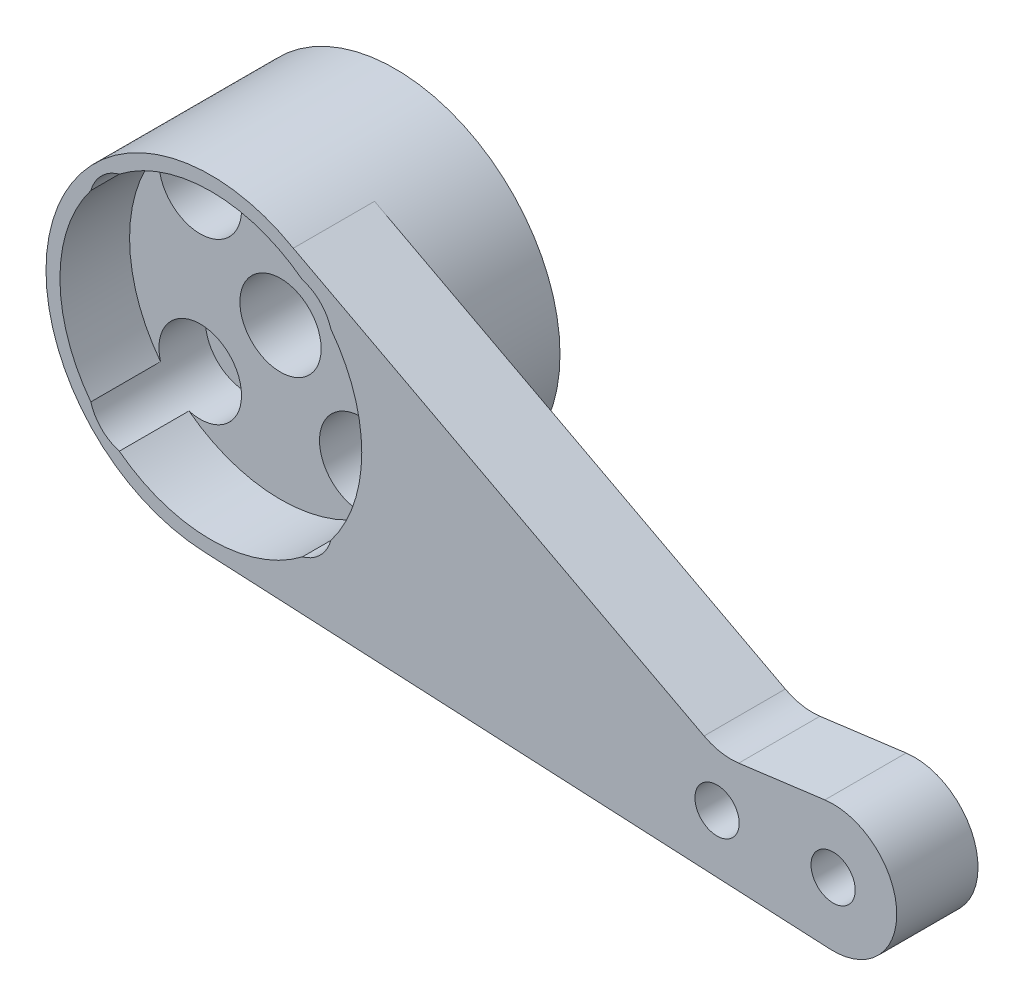
SolidWorks part; units mm, degrees
ref_plane "Front Plane" through (0, 0, 0) normal (0, 0, 1) x (1, 0, 0)
ref_plane "Top Plane" through (0, 0, 0) normal (0, 1, 0) x (1, 0, 0)
ref_plane "Right Plane" through (0, 0, 0) normal (1, 0, 0) x (0, 0, -1)
ref_plane "Plane1" through (0, 0, 0) normal (0, 0, -1) x (-1, 0, 0)
sketch "Sketch1" plane through (0, 0, 0) normal (0, 0, -1) x (-1, 0, 0)
  line L0 (-54.9006, 0.2614) -> (-46.1167, 9.6815) construction
  line L1 (-54.6285, -5.2121) -> (-0.5934, -2.5259)
  line L3 (-54.9006, 0.2614) -> (-1.2984, 11.6566) construction
  line L4 (-8.3993, 23.9536) -> (-43.781, 5.2606)
  line L5 (-46.7655, 4.7237) -> (-54.1894, 5.6953)
  circle A0 centre (-46.1167, 9.6815) radius 4 construction
  arc A2 (-54.1894, 5.6953) -> (-54.6285, -5.2121) centre (-54.9006, 0.2614) ccw
  arc A3 (-0.5934, -2.5259) -> (-8.3993, 23.9536) centre (-1.2984, 11.6566) ccw
  arc A4 (-46.7655, 4.7237) -> (-43.781, 5.2606) centre (-46.1167, 9.6815) ccw
  dimension "D2" = 14.2
  dimension "D3" = 12.88
  dimension "D5" = 35
  dimension "D6" = 8
  dimension "D7" = 10
  dimension "D1" = 54.8
extrude "Boss-Extrude1" add sketch "Sketch1" against normal blind 15
sketch "Sketch10" plane through (0, 0, 0) normal (0, 0, -1) x (-1, 0, 0)
  circle A0 centre (-1.2984, 11.6566) radius 14.2
  arc A1 (-0.5934, -2.5259) -> (-8.3993, 23.9536) centre (-1.2984, 11.6566) ccw construction
  circle A2 centre (-54.9006, 0.2614) radius 5.4803
  arc A3 (-54.1894, 5.6953) -> (-54.6285, -5.2121) centre (-54.9006, 0.2614) ccw construction
  point P5 (-1.2984, 11.6566)
hole_wizard "CBORE for M6 Hex Head Bolt1" positions "Sketch7" profile "Sketch6" counterbore size "M6" standard "Ansi Metric" end condition through all
sketch "Sketch7" plane through (0, 0, 0) normal (0, 0, -1) x (-1, 0, 0)
  point P0 (-1.2984, 11.6566)
sketch "Sketch6" plane through (1.2984, 11.6566, 0) normal (1, 0, 0) x (0, 1, 0)
  line L0 (0, 0) -> (0, 15)
  line L1 (0, 15) -> (3.5, 15)
  line L3 (3.5, 15) -> (3.5, 3)
  line L4 (3.5, 3) -> (12.8, 3)
  line L5 (12.8, 3) -> (12.8, 0)
  line L7 (12.8, 0) -> (0, 0)
  line L11 (0, -6.35) -> (0, 107.95) construction
  dimension "Thru Hole Dia." = 7
  dimension "Thru Hole Depth" = 15
  dimension "C'Bore Dia." = 25.6
  dimension "C'Bore Depth" = 3
ref_plane "Plane4" through (0, 0, 7.5) normal (0, 0, -1) x (-1, 0, 0)
sketch "Sketch30" plane through (0, 0, 15) normal (0, 0, 1) x (1, 0, 0)
  line L1 (68.7065, -22.2417) -> (-19.1857, -22.2417)
  line L2 (68.7065, -22.2417) -> (68.7065, 41.145)
  line L3 (68.7065, 41.145) -> (-19.1857, 41.145)
  line L4 (-19.1857, -22.2417) -> (-19.1857, 41.145)
extrude "Cut-Extrude8" cut sketch "Sketch30" against normal blind 0.125
sketch "Sketch31" plane through (0, 0, 0) normal (0, 0, -1) x (-1, 0, 0)
  line L1 (-64.611, 30.1264) -> (17.734, 30.1264)
  line L2 (-64.611, 30.1264) -> (-64.611, -8.8981)
  line L3 (-64.611, -8.8981) -> (17.734, -8.8981)
  line L4 (17.734, 30.1264) -> (17.734, -8.8981)
extrude "Cut-Extrude9" cut sketch "Sketch31" against normal blind 0.125
sketch "Sketch38" plane through (0, 0, 14.875) normal (0, 0, 1) x (1, 0, 0)
  circle A0 centre (1.2984, 11.6566) radius 3.5 construction
  circle A1 centre (1.2984, 11.6566) radius 3.5
  circle A2 centre (-5.616, 18.5718) radius 1.905
  circle A3 centre (8.2136, 18.571) radius 1.905
  circle A4 centre (8.2128, 4.7414) radius 1.905
  circle A5 centre (-5.6168, 4.7422) radius 1.905
  line B0 (3.7785, 13.3445) -> (3.7783, 9.9684)
  line B1 (-14.7035, 12.2926) -> (-1.6336, 12.2918)
  line B2 (-14.7033, 16.4201) -> (-14.7035, 12.2926)
  line B3 (-11.9069, 16.4199) -> (-14.7033, 16.4201)
  line B4 (-11.2749, 6.8948) -> (-11.2749, 6.8267)
  line B5 (-14.7039, 6.8951) -> (-11.2749, 6.8948)
  line B6 (-14.7036, 11.0226) -> (-14.7039, 6.8951)
  line B7 (-1.6336, 11.0218) -> (-14.7036, 11.0226)
  arc B8 (2.6475, 8.977) -> (3.7783, 9.9684) centre (2.7783, 9.9684) ccw
  arc B9 (3.7785, 13.3445) -> (2.6478, 14.336) centre (2.7785, 13.3446) ccw
  arc B10 (2.6478, 14.336) -> (-1.6336, 12.2918) centre (1.2984, 11.6566) ccw
  arc B11 (-11.9069, 16.4199) -> (-8.9599, 19.0076) centre (-11.9068, 19.3917) ccw
  arc B12 (-4.0299, 21.5478) -> (-8.9599, 19.0076) centre (-5.616, 18.5718) ccw
  arc B13 (-4.0299, 21.5478) -> (-1.7731, 21.3412) centre (-2.6561, 24.1255) ccw
  arc B14 (4.3711, 21.3408) -> (-1.7731, 21.3412) centre (1.2984, 11.6566) ccw
  arc B15 (4.3711, 21.3408) -> (6.628, 21.5471) centre (5.2545, 24.1251) ccw
  arc B16 (11.1896, 16.985) -> (6.628, 21.5471) centre (8.2136, 18.571) ccw
  arc B17 (11.1896, 16.985) -> (10.983, 14.7281) centre (13.7674, 15.6111) ccw
  arc B18 (10.9827, 8.5839) -> (10.983, 14.7281) centre (1.2984, 11.6566) ccw
  arc B19 (10.9827, 8.5839) -> (11.189, 6.3271) centre (13.7669, 7.7006) ccw
  arc B20 (6.6268, 1.7654) -> (11.189, 6.3271) centre (8.2128, 4.7414) ccw
  arc B21 (6.6268, 1.7654) -> (4.3699, 1.972) centre (5.253, -0.8123) ccw
  arc B22 (-1.7742, 1.9724) -> (4.3699, 1.972) centre (1.2984, 11.6566) ccw
  arc B23 (-1.7742, 1.9724) -> (-4.0311, 1.7661) centre (-2.6576, -0.8119) ccw
  arc B24 (-8.9608, 4.3068) -> (-4.0311, 1.7661) centre (-5.6168, 4.7422) ccw
  arc B25 (-8.9608, 4.3068) -> (-11.2749, 6.8267) centre (-11.9077, 3.9231) ccw
  arc B26 (-1.6336, 11.0218) -> (2.6475, 8.977) centre (1.2984, 11.6566) ccw
  dimension "D1" = 3.81
sketch_block_instance "Block1-1"
sketch_block "Block1"
extrude "Cut-Extrude10" cut sketch "Sketch38" against normal through all contours A2 | A3 | A4 | A5
sketch "Sketch39" plane through (0, 0, 0.125) normal (0, 0, -1) x (-1, 0, 0)
  circle A1 centre (-1.2984, 11.6566) radius 12.8 construction
  circle A2 centre (-1.2984, 11.6566) radius 12.8
extrude "Cut-Extrude11" cut sketch "Sketch39" against normal offset from surface (7.75 mm away) 7 flip side to cut contours A2 up to face at (-3.7118, 4.7422, 14.875)
sketch "Sketch40" plane through (0, 0, 14.875) normal (0, 0, 1) x (1, 0, 0)
  circle A0 centre (1.2984, 11.6566) radius 13
  dimension "D1" = 26
extrude "Cut-Extrude12" cut sketch "Sketch40" against normal offset from surface (6 mm away) 1 up to face at (32.9108, 6.1436, 7.875)
sketch "Sketch41" plane through (0, 0, 3) normal (0, 0, -1) x (-1, 0, 0)
  circle A1 centre (-1.2984, 11.6566) radius 12.8
  circle A4 centre (-1.2984, 11.6566) radius 12.8
  dimension "D1" = 0
extrude "Boss-Extrude2" add sketch "Sketch41" along normal blind 4
sketch "Sketch42" plane through (0, 0, 3) normal (0, 0, 1) x (1, 0, 0)
  circle A0 centre (8.2128, 4.7414) radius 1.905 construction
  circle A1 centre (1.2984, 11.6566) radius 3.5
  circle A2 centre (1.2984, 11.6566) radius 3.5
  circle A3 centre (-5.6168, 4.7422) radius 1.905 construction
  circle A4 centre (-5.616, 18.5718) radius 1.905 construction
  circle A5 centre (8.2136, 18.571) radius 1.905 construction
  circle A6 centre (8.2128, 4.7414) radius 1.905
  circle A7 centre (-5.6168, 4.7422) radius 1.905
  circle A8 centre (-5.616, 18.5718) radius 1.905
  circle A9 centre (8.2136, 18.571) radius 1.905
  dimension "D1" = 0
extrude "Cut-Extrude13" cut sketch "Sketch42" against normal through all
sketch "Sketch43" plane through (0, 0, 7.875) normal (0, 0, -1) x (-1, 0, 0)
  circle A0 centre (-1.2984, 11.6566) radius 12.8
  circle A1 centre (-1.2984, 11.6566) radius 14.2
extrude "Boss-Extrude3" add sketch "Sketch43" along normal through all
sketch "Sketch44" plane through (0, 0, 8.875) normal (0, 0, 1) x (1, 0, 0)
  circle A0 centre (8.2136, 18.571) radius 3.556
  circle A1 centre (-5.616, 18.5718) radius 3.556
  circle A2 centre (-5.6168, 4.7422) radius 3.556
  circle A3 centre (8.2128, 4.7414) radius 3.556
  dimension "D1" = 7.112
extrude "Cut-Extrude14" cut sketch "Sketch44" along normal through all and the other way blind 4
sketch "Sketch45" plane through (0, 0, 7.875) normal (0, 0, -1) x (-1, 0, 0)
  line L0 (-54.9006, 0.2614) -> (-44.9006, 0.2614) construction
  circle A0 centre (-54.9006, 0.2614) radius 1.905
  circle A1 centre (-44.9006, 0.2614) radius 1.905
  arc A2 (-54.1894, 5.6953) -> (-54.6285, -5.2121) centre (-54.9006, 0.2614) ccw construction
  dimension "D1" = 3.81
  dimension "D2" = 10
extrude "Cut-Extrude15" cut sketch "Sketch45" against normal through all
sketch "Sketch46" plane through (0, 0, 7.875) normal (0, 0, -1) x (-1, 0, 0)
  circle A0 centre (-54.9006, 0.2614) radius 3.556
  circle A1 centre (-44.9006, 0.2614) radius 3.556
  dimension "D1" = 7.112
extrude "Cut-Extrude16" cut sketch "Sketch46" against normal blind 2
sketch "Sketch47" plane through (0, 0, 7.875) normal (0, 0, -1) x (-1, 0, 0)
  line L1 (-54.9006, 2.1664) -> (-44.9006, 2.1664)
  line L2 (-54.9006, 2.1664) -> (-54.9006, -1.6436)
  line L3 (-54.9006, -1.6436) -> (-44.9006, -1.6436)
  line L4 (-44.9006, 2.1664) -> (-44.9006, -1.6436)
  circle A0 centre (-54.9006, 0.2614) radius 1.905 construction
  circle A1 centre (-44.9006, 0.2614) radius 1.905 construction
extrude "Cut-Extrude17" cut sketch "Sketch47" against normal blind 2
